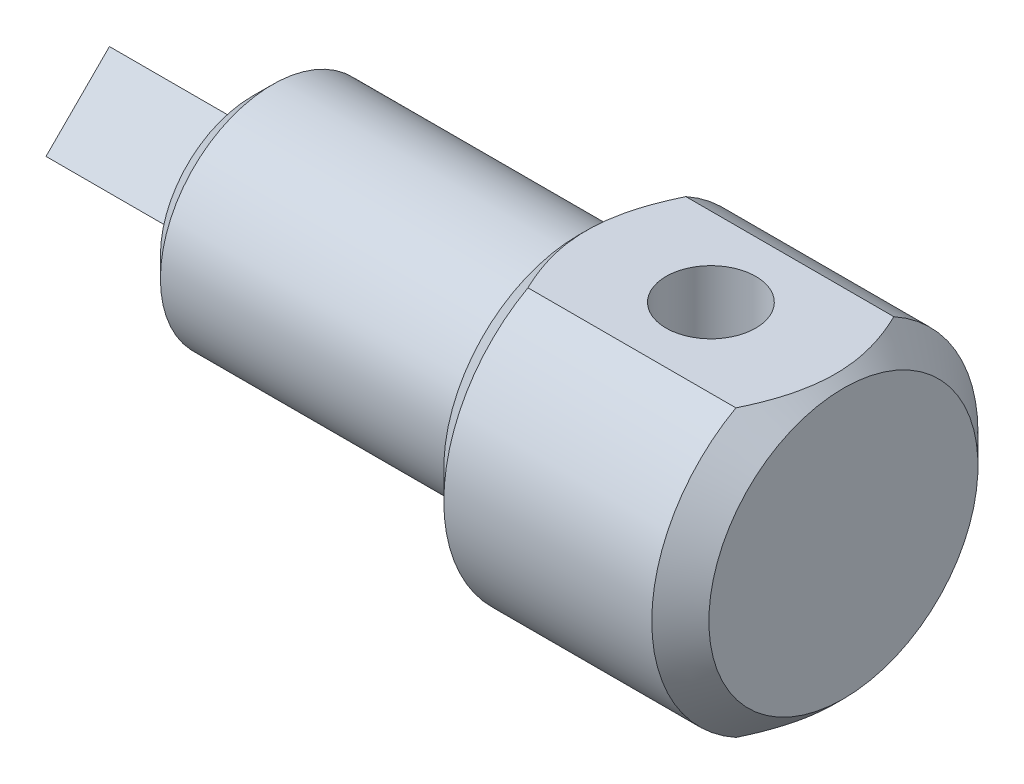
SolidWorks part; units mm, degrees
ref_plane "Спереди" through (0, 0, 0) normal (0, 0, 1) x (1, 0, 0)
ref_plane "Сверху" through (0, 0, 0) normal (0, 1, 0) x (1, 0, 0)
ref_plane "Справа" through (0, 0, 0) normal (1, 0, 0) x (0, 0, -1)
sketch "Эскиз1" plane through (0, 0, 0) normal (0, 0, 1) x (1, 0, 0)
  line L0 (0, 0) -> (-9.5781, 0) construction
  line L1 (0, 0) -> (0, 27.5)
  line L2 (0, 27.5) -> (80, 27.5)
  line L3 (80, 27.5) -> (80, 40)
  line L4 (80, 40) -> (145, 40)
  line L5 (145, 40) -> (145, 0)
  line L6 (145, 0) -> (0, 0)
  dimension "D1" = 145
  dimension "D2" = 80
  dimension "D3" = 80
  dimension "D4" = 55
revolve "Повернуть1" add sketch "Эскиз1" angle 360 about L0
sketch "Эскиз3" plane through (0, 0, 0) normal (-1, 0, 0) x (0, 0, 1)
  line L0 (0, 27.5) -> (0, -27.5) construction
  line L1 (-27.5, 0) -> (27.5, 0) construction
  line L2 (0, -15.5563) -> (-15.5563, 0)
  line L3 (0, -15.5563) -> (15.5563, 0)
  line L4 (-15.5563, 0) -> (0, 15.5563)
  line L5 (15.5563, 0) -> (0, 15.5563)
  line L6 (0, -15.5563) -> (0, 15.5563) construction
  line L7 (-15.5563, 0) -> (15.5563, 0) construction
  circle A0 centre (0, 0) radius 27.5 construction
  circle A1 centre (0, 0) radius 27.5 construction
  point P9 (0, 13.8067)
  point P10 (0, 0)
  dimension "D1" = 22
extrude "Бобышка-Вытянуть1" add sketch "Эскиз3" along normal blind 35
sketch "Эскиз4" plane through (0, 0, 0) normal (0, 1, 0) x (1, 0, 0)
  line L0 (80, 27.5) -> (0, 27.5) construction
  line L1 (15, 27.5) -> (60, 27.5)
  line L2 (15, 27.5) -> (15, 22.5)
  line L3 (15, 22.5) -> (60, 22.5)
  line L4 (60, 27.5) -> (60, 22.5)
  line L6 (0, 27.5) -> (0, -27.5) construction
  dimension "D1" = 45
  dimension "D2" = 5
  dimension "D3" = 15
extrude "Вырез-Вытянуть1" cut sketch "Эскиз4" against normal mid plane 16
sketch "Эскиз5" plane through (145, 0, 0) normal (1, 0, 0) x (0, 0, -1)
  line L0 (-19.3649, 35) -> (19.3649, 35)
  line L1 (-40, 0) -> (40, 0) construction
  circle A0 centre (0, 0) radius 40 construction
  dimension "D1" = 70
extrude "Вырез-Вытянуть2" cut sketch "Эскиз5" against normal through all and the other way through all
mirror "Зеркальное отражение1" about plane through (0, 0, 0) normal (0, 1, 0) of "Вырез-Вытянуть2"
sketch "Эскиз6" plane through (0, 35, 0) normal (0, 1, 0) x (1, 0, 0)
  line L0 (80, 40) -> (80, 19.3649) construction
  line L1 (80, 0) -> (145, 0) construction
  line L2 (80, 27.5) -> (80, -27.5) construction
  line L3 (145, 19.3649) -> (145, -19.3649) construction
  circle A0 centre (112.5, 0) radius 11
  point P10 (112.5, 0)
  point P11 (0, 0)
  dimension "D2" = 22
  dimension "D1" = 32.5
extrude "Вырез-Вытянуть3" cut sketch "Эскиз6" against normal through all both and the other way through all
chamfer "Фаска1" distance 7 angle 45 2 edges at (145, 0, -40) (80, 0, -40)
chamfer "Фаска2" distance 5 angle 45 1 edges at (0, 0, -27.5)
